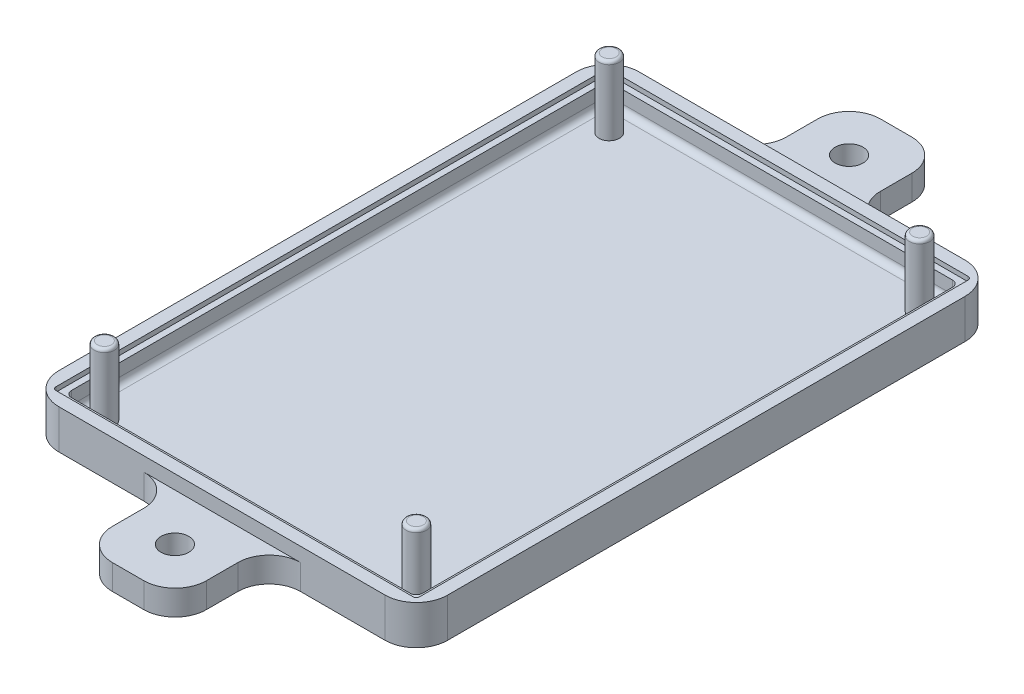
SolidWorks part; units mm, degrees
ref_plane "Front Plane" through (0, 0, 0) normal (0, 0, 1) x (1, 0, 0)
ref_plane "Top Plane" through (0, 0, 0) normal (0, 1, 0) x (1, 0, 0)
ref_plane "Right Plane" through (0, 0, 0) normal (1, 0, 0) x (0, 0, -1)
sketch "Sketch1" plane through (0, 0, 0) normal (0, 1, 0) x (1, 0, 0)
  line L0 (-30.226, 45.72) -> (-30.226, -45.72)
  line L1 (-28.956, 44.45) -> (28.956, 44.45)
  line L2 (-28.956, 44.45) -> (-28.956, -44.45)
  line L3 (-28.956, -44.45) -> (28.956, -44.45)
  line L4 (28.956, 44.45) -> (28.956, -44.45)
  line L5 (-28.956, 44.45) -> (28.956, -44.45) construction
  line L6 (-28.956, -44.45) -> (28.956, 44.45) construction
  line L7 (-30.226, -45.72) -> (30.226, -45.72)
  line L8 (30.226, 45.72) -> (30.226, -45.72)
  line L9 (-30.226, 45.72) -> (30.226, 45.72)
  line L10 (-32.766, 48.26) -> (32.766, 48.26)
  line L11 (32.766, 48.26) -> (32.766, -48.26)
  line L12 (-32.766, -48.26) -> (32.766, -48.26)
  line L13 (-32.766, 48.26) -> (-32.766, -48.26)
  point P0 (0, 0)
  dimension "D3" = 1.27
  dimension "D4" = 2.54
  dimension "D1" = 88.9
  dimension "D2" = 57.912
extrude "Boss-Extrude4" add sketch "Sketch1" along normal blind 2.54 contours L0 L7 L8 L9
sketch "Sketch7" plane through (0, 0, 0) normal (0, -1, 0) x (1, 0, 0)
  line L0 (32.766, -48.26) -> (32.766, 48.26)
  line L1 (30.226, -45.72) -> (-30.226, -45.72)
  line L2 (30.226, -45.72) -> (30.226, 45.72)
  line L3 (30.226, 45.72) -> (-30.226, 45.72)
  line L4 (-30.226, -45.72) -> (-30.226, 45.72)
  line L5 (32.766, 48.26) -> (-32.766, 48.26)
  line L6 (-32.766, -48.26) -> (-32.766, 48.26)
  line L7 (32.766, -48.26) -> (-32.766, -48.26)
  dimension "D1" = 2.54
extrude "Boss-Extrude5" add sketch "Sketch7" against normal blind 6.35
sketch "Sketch8" plane through (0, 2.54, 0) normal (0, 1, 0) x (1, 0, 0)
  line L10 (-28.448, 43.942) -> (-28.448, -43.942)
  line L11 (-30.226, 45.72) -> (30.226, 45.72)
  line L12 (-30.226, 45.72) -> (-30.226, -45.72)
  line L13 (-30.226, -45.72) -> (30.226, -45.72)
  line L14 (-32.004, -47.498) -> (32.004, -47.498)
  line L15 (32.004, -47.498) -> (32.004, 47.498)
  line L16 (-32.004, 47.498) -> (-32.004, -47.498)
  line L17 (32.004, 47.498) -> (-32.004, 47.498)
  line L18 (-32.004, -47.498) -> (32.004, -47.498)
  line L19 (32.004, -47.498) -> (32.004, 47.498)
  line L20 (-32.004, 47.498) -> (-32.004, -47.498)
  line L21 (32.004, 47.498) -> (-32.004, 47.498)
  line L22 (30.226, 45.72) -> (30.226, -45.72)
  line L23 (-28.448, -43.942) -> (28.448, -43.942)
  line L24 (28.448, 43.942) -> (28.448, -43.942)
  line L25 (-28.448, 43.942) -> (28.448, 43.942)
  circle A0 centre (-24.13, 39.878) radius 1.651
  circle A1 centre (26.162, 39.878) radius 1.651
  circle A2 centre (-24.638, -41.402) radius 1.651
  circle A3 centre (25.908, -41.402) radius 1.651
  dimension "D3" = 3.302
  dimension "D4" = 3.302
  dimension "D5" = 3.302
  dimension "D6" = 3.302
  dimension "D8" = 5.842
  dimension "D9" = 5.842
  dimension "D10" = 4.064
  dimension "D11" = 4.318
  dimension "D12" = 4.318
  dimension "D13" = 5.588
  dimension "D14" = 4.318
  dimension "D7" = 6.096
  dimension "D1" = 1.778
  dimension "D2" = 1.778
extrude "Boss-Extrude6" add sketch "Sketch8" along normal blind 11.176 contours A0 | A2 | A1 | A3
sketch "Sketch10" plane through (0, 2.54, 0) normal (0, 1, 0) x (1, 0, 0)
  line L0 (28.448, -43.942) -> (28.448, 43.942)
  line L1 (30.226, -45.72) -> (-30.226, -45.72)
  line L2 (30.226, -45.72) -> (30.226, 45.72)
  line L3 (30.226, 45.72) -> (-30.226, 45.72)
  line L4 (-30.226, -45.72) -> (-30.226, 45.72)
  line L5 (28.448, 43.942) -> (-28.448, 43.942)
  line L6 (-28.448, -43.942) -> (-28.448, 43.942)
  line L7 (28.448, -43.942) -> (-28.448, -43.942)
  dimension "D1" = 1.778
extrude "Boss-Extrude7" add sketch "Sketch10" along normal blind 3.048
sketch "Sketch13" plane through (0, 5.588, 0) normal (0, 1, 0) x (1, 0, 0)
  line L10 (-30.226, -45.72) -> (30.226, -45.72) construction
  line L11 (-30.226, 45.72) -> (30.226, 45.72)
  line L12 (-30.226, 45.72) -> (-30.226, -45.72)
  line L13 (-30.226, -45.72) -> (30.226, -45.72)
  line L14 (29.464, -44.958) -> (29.464, 44.958)
  line L15 (-29.464, -44.958) -> (29.464, -44.958)
  line L16 (-29.464, 44.958) -> (-29.464, -44.958)
  line L17 (29.464, 44.958) -> (-29.464, 44.958)
  line L18 (29.464, -44.958) -> (29.464, 44.958)
  line L19 (-29.464, -44.958) -> (29.464, -44.958)
  line L20 (-29.464, 44.958) -> (-29.464, -44.958)
  line L21 (29.464, 44.958) -> (-29.464, 44.958)
  line L22 (30.226, 45.72) -> (30.226, -45.72)
  dimension "D1" = 0.762
extrude "Boss-Extrude8" add sketch "Sketch13" along normal blind 0.762
sketch "Sketch14" plane through (0, 0, 0) normal (0, -1, 0) x (1, 0, 0)
  line L0 (-31.496, -46.99) -> (-31.496, 46.99)
  line L1 (-32.766, -48.26) -> (32.766, -48.26)
  line L2 (-32.766, -48.26) -> (-32.766, 48.26)
  line L3 (-32.766, 48.26) -> (32.766, 48.26)
  line L4 (32.766, -48.26) -> (32.766, 48.26)
  line L5 (-31.496, 46.99) -> (31.496, 46.99)
  line L6 (31.496, -46.99) -> (31.496, 46.99)
  line L7 (-31.496, -46.99) -> (31.496, -46.99)
  dimension "D1" = 1.27
extrude "Cut-Extrude1" cut sketch "Sketch14" against normal up to next
fillet "Fillet1" radius 5.08 4 edges at (31.496, 3.175, -46.99) (-31.496, 3.175, -46.99) (-31.496, 3.175, 46.99) (31.496, 3.175, 46.99)
fillet "Fillet3" radius 0.508 4 edges at (26.162, 13.716, -38.227) (-24.13, 13.716, -38.227) (-24.638, 13.716, 43.053) (25.908, 13.716, 43.053)
fillet "Fillet4" radius 0.508 4 edges at (-29.464, 5.969, -44.958) (-29.464, 5.969, 44.958) (29.464, 5.969, 44.958) (29.464, 5.969, -44.958)
fillet "Fillet5" radius 1.016 8 edges at (-28.448, 4.064, -43.942) (-28.448, 2.54, 0) (-28.448, 4.064, 43.942) (0, 2.54, 43.942) (28.448, 4.064, 43.942) (28.448, 4.064, -43.942) (0, 2.54, -43.942) (28.448, 2.54, 0)
sketch "Sketch16" plane through (0, 0, 0) normal (0, -1, 0) x (1, 0, 0)
  line L0 (0, 46.99) -> (0, 62.23)
  line L1 (26.416, 46.99) -> (-26.416, 46.99) construction
  line L2 (0, 46.99) -> (0, -46.99)
  line L3 (0, 46.99) -> (-7.5887, 46.99)
  line L4 (0, 46.99) -> (0, 62.23)
  line L5 (0, 62.23) -> (-7.5887, 62.23)
  line L6 (-7.5887, 46.99) -> (-7.5887, 62.23)
  line L7 (-7.5887, 62.23) -> (7.6513, 62.23)
  line L8 (-7.5887, 62.23) -> (-7.5887, 46.99)
  line L9 (-7.5887, 46.99) -> (7.6513, 46.99)
  line L10 (7.6513, 62.23) -> (7.6513, 46.99)
  line L11 (-26.416, -46.99) -> (26.416, -46.99) construction
  line L12 (0, -46.99) -> (7.62, -46.99)
  line L13 (0, -46.99) -> (0, -54.61)
  line L14 (7.62, -46.99) -> (-7.62, -46.99)
  line L15 (7.62, -46.99) -> (7.62, -62.23)
  line L16 (7.62, -62.23) -> (-7.62, -62.23)
  line L17 (-7.62, -46.99) -> (-7.62, -62.23)
  circle A0 centre (0, 54.61) radius 2.2479
  circle A1 centre (0, -54.61) radius 2.2479
  dimension "D3" = 4.4958
  dimension "D9" = 4.4958
  dimension "D1" = 15.24
  dimension "D2" = 15.24
  dimension "D4" = 7.62
  dimension "D5" = 7.62
  dimension "D6" = 15.24
  dimension "D7" = 15.24
  dimension "D8" = 7.62
extrude "Boss-Extrude9" add sketch "Sketch16" against normal blind 4.064
fillet "Fillet8" radius 5.08 8 edges at (-7.62, 2.032, -46.99) (-7.62, 2.032, -62.23) (7.62, 2.032, -62.23) (7.62, 2.032, -46.99) (7.6513, 2.032, 46.99) (7.6513, 2.032, 62.23) (-7.5887, 2.032, 62.23) (-7.5887, 2.032, 46.99)
